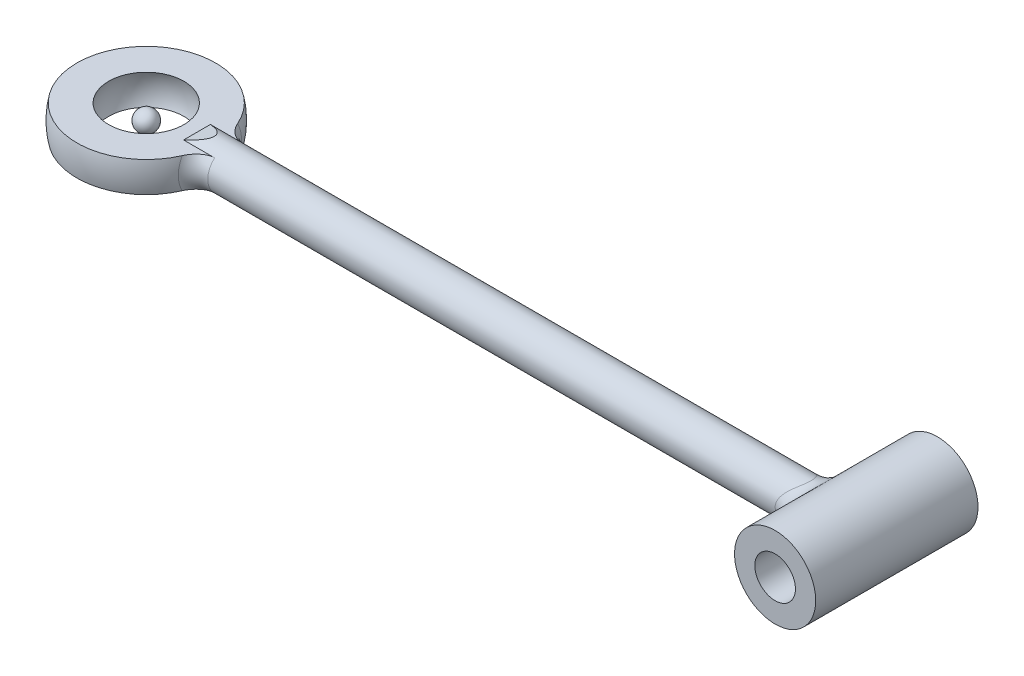
SolidWorks part; units mm, degrees
ref_plane "前视基准面" through (0, 0, 0) normal (0, 0, 1) x (1, 0, 0)
ref_plane "上视基准面" through (0, 0, 0) normal (0, 1, 0) x (1, 0, 0)
ref_plane "右视基准面" through (0, 0, 0) normal (1, 0, 0) x (0, 0, -1)
other "Configuration Table"
sketch "草图1" plane through (0, 0, 0) normal (0, 0, 1) x (1, 0, 0)
  line L0 (0, 0.75) -> (0, -0.75) construction
  line L1 (5, -0.75) -> (-5, -0.75)
  line L2 (5, -0.75) -> (5, 0.75)
  line L3 (5, 0.75) -> (-5, 0.75)
  line L4 (-5, -0.75) -> (-5, 0.75)
  line L5 (5, -0.75) -> (-5, 0.75) construction
  line L6 (5, 0.75) -> (-5, -0.75) construction
  circle A0 centre (0, 0) radius 3.5
  circle A1 centre (0, 0) radius 2
  dimension "D1" = 4
  dimension "D2" = 1.5
  dimension "D3" = 1.5
  dimension "D4" = 10
revolve "旋转1" add sketch "草图1" angle 360 about L0 region at (-2.7121, 0, 0)
sketch "草图2" plane through (0, 0, 0) normal (0, 0, 1) x (1, 0, 0)
  line L0 (0, 0) -> (35, 0) construction
  circle A0 centre (35, 0) radius 1
  circle A1 centre (35, 0) radius 2
  dimension "D2" = 2
  dimension "D3" = 1
  dimension "D1" = 35
extrude "凸台-拉伸1" add sketch "草图2" along normal mid plane 8 separate body
sketch "草图3" plane through (0, 0, 0) normal (0, 1, 0) x (1, 0, 0)
  line L0 (-0.5, 0) -> (0.5, 0)
  line L1 (37, 4) -> (33, 4) construction
  line L2 (35, 4) -> (35, 0) construction
  line L3 (35, 0) -> (0, 0) construction
  line L4 (2.5, 0) -> (33.9, 0)
  line L5 (2.5, 0) -> (2.5, 1)
  line L6 (2.5, 1) -> (33.9, 1)
  line L7 (33.9, 0) -> (33.9, 1)
  arc A0 (0.5, 0) -> (-0.5, 0) centre (0, 0) ccw
  dimension "D4" = 1
  dimension "D1" = 1
  dimension "D2" = 2.5
  dimension "D3" = 1.1
revolve "旋转2" add sketch "草图3" angle 360 about L4
sketch "草图4" plane through (0, 0, 0) normal (0, 0, 1) x (1, 0, 0)
  line L0 (2.5, 0.75) -> (2.5, 1)
  line L1 (2.5, 1) -> (3.3541, 1)
  line L2 (3.3541, 1) -> (2.5, 0.75)
  line L3 (3.3541, -0.75) -> (3.3541, 0.75) construction
  line L4 (0, 0) -> (3.8322, 0) construction
  line L5 (3.3541, -1) -> (2.5, -0.75)
  line L6 (2.5, -1) -> (3.3541, -1)
  line L7 (2.5, -0.75) -> (2.5, -1)
extrude "切除-拉伸1" cut sketch "草图4" against normal mid plane 10
fillet "圆角1" radius 1 3 edges at (33.0025, 0.1009, -0.9949) (3.3541, 0, -1) (3.3541, 0, 1)
